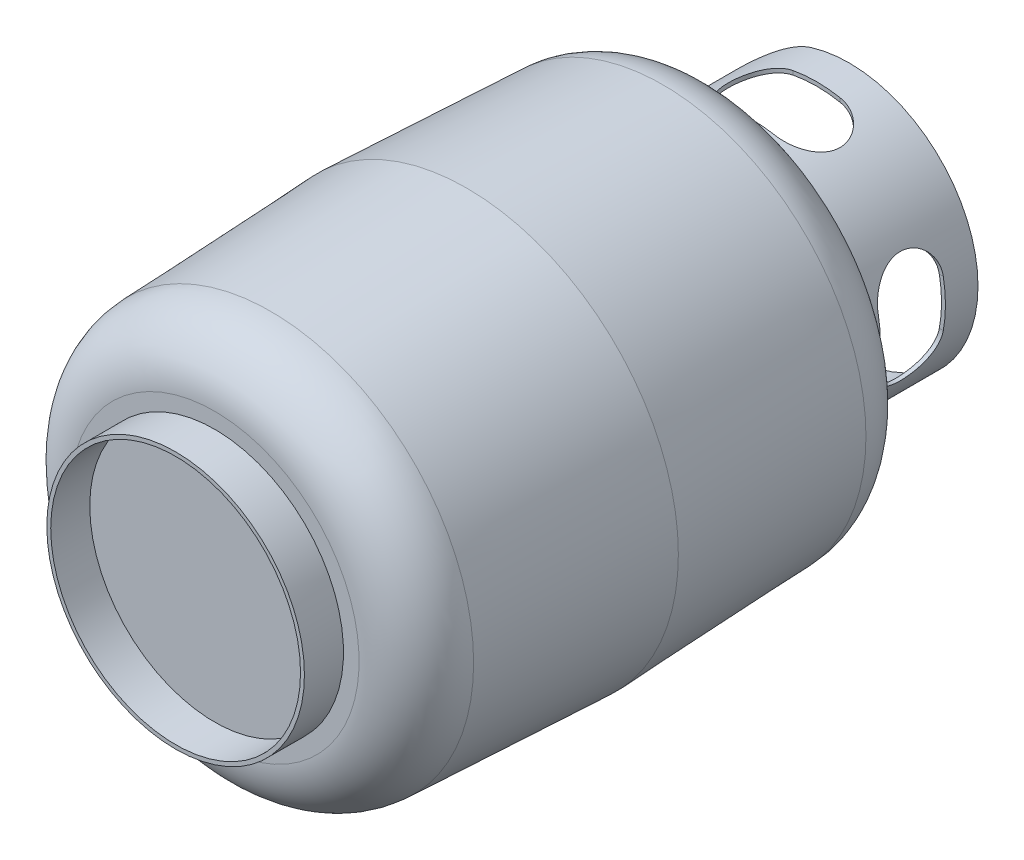
SolidWorks part; units mm, degrees
material "1060 Alloy"
ref_plane "Front Plane" through (0, 0, 0) normal (0, 0, 1) x (1, 0, 0)
ref_plane "Top Plane" through (0, 0, 0) normal (0, 1, 0) x (1, 0, 0)
ref_plane "Right Plane" through (0, 0, 0) normal (1, 0, 0) x (0, 0, -1)
sketch "Sketch1" plane through (0, 0, 0) normal (0, 1, 0) x (1, 0, 0)
  line L0 (0, 288.0587) -> (0, -288.0587) construction
  line L1 (-201.8145, 0) -> (201.8145, 0) construction
  line L2 (0, -193.75) -> (110.9626, -193.75)
  line L3 (155.9197, -150.7129) -> (162.5, 0)
  line L4 (162.5, 0) -> (155.9197, 150.7129)
  line L5 (110.9626, 193.75) -> (37, 193.75)
  line L6 (25, 205.75) -> (25, 213.75)
  line L7 (0, -189.75) -> (110.9626, -189.75)
  line L8 (0, -193.75) -> (0, 213.75) construction
  line L9 (151.9235, -150.5384) -> (158.4962, 0)
  line L10 (158.4962, 0) -> (151.9235, 150.5384)
  line L11 (110.9626, 189.75) -> (37, 189.75)
  line L12 (21, 205.75) -> (21, 213.75)
  line L13 (21, 213.75) -> (25, 213.75)
  line L14 (0, -189.75) -> (0, -193.75)
  arc A0 (155.9197, -150.7129) -> (110.9626, -193.75) centre (110.9626, -148.75) cw
  arc A1 (110.9626, 193.75) -> (155.9197, 150.7129) centre (110.9626, 148.75) cw
  arc A2 (25, 205.75) -> (37, 193.75) centre (37, 205.75) ccw
  arc A3 (151.9235, -150.5384) -> (110.9626, -189.75) centre (110.9626, -148.75) cw
  arc A4 (110.9626, 189.75) -> (151.9235, 150.5384) centre (110.9626, 148.75) cw
  arc A5 (21, 205.75) -> (37, 189.75) centre (37, 205.75) ccw
  point P4 (0, 0)
  point P8 (0, 0)
  point P16 (154.0407, 193.75)
  dimension "D3" = 45
  dimension "D5" = 12
  dimension "D8" = 301.4257
  dimension "D1" = 25
  dimension "D2" = 387.5
  dimension "D4" = 92.5
  dimension "D6" = 20
  dimension "D7" = 162.5
  dimension "D9" = 137.5
  dimension "D10" = 4
revolve "Revolve2" add sketch "Sketch1" angle 360 about L0
sketch "Sketch5" plane through (0, 0, 193.75) normal (0, 0, 1) x (1, 0, 0)
  circle A0 centre (0, 0) radius 98.9626
  circle A1 centre (0, 0) radius 95.9626
  circle A2 centre (0, 0) radius 110.9626 construction
  dimension "D1" = 12
  dimension "D2" = 3
extrude "Boss-Extrude1" add sketch "Sketch5" along normal blind 30
sketch "Sketch6" plane through (0, 0, -193.75) normal (0, 0, -1) x (-1, 0, 0)
  line L0 (-98.9626, 0) -> (98.9626, 0) construction
  line L1 (0, 98.9626) -> (0, -98.9626) construction
  line L2 (0, 0) -> (56.7626, 81.0654) construction
  line L3 (0, 0) -> (56.7626, -81.0654) construction
  line L4 (56.7626, 81.0654) -> (55.0419, 78.6079)
  line L5 (55.0419, -78.6079) -> (56.7626, -81.0654)
  arc A0 (56.7626, 81.0654) -> (56.7626, -81.0654) centre (0, 0) ccw
  arc A1 (55.0419, 78.6079) -> (55.0419, -78.6079) centre (0, 0) ccw
  circle A2 centre (0, 0) radius 110.9626 construction
  point P9 (0, 0)
  point P12 (0, 0)
  dimension "D1" = 12
  dimension "D2" = 3
  dimension "D3" = 55
extrude "Boss-Extrude2" add sketch "Sketch6" along normal blind 100
fillet "Fillet1" radius 30 2 edges at (-55.9022, 79.8367, -293.75) (-55.9022, -79.8367, -293.75)
sketch "Sketch7" plane through (0, 0, 0) normal (0, 1, 0) x (1, 0, 0)
  line L0 (0, -317.6654) -> (0, 317.6654) construction
  line L1 (310.6091, 0) -> (-310.6091, 0) construction
  line L2 (-220.5391, 243.75) -> (220.5391, 243.75) construction
  line L3 (95.9626, 293.75) -> (-27.7085, 293.75) construction
  line L4 (-18, 269.7278) -> (-18, 217.7722) construction
  line L5 (18, 269.7278) -> (18, 217.7722) construction
  line L6 (-18, 268.75) -> (18, 268.75)
  line L7 (-18, 218.75) -> (18, 218.75)
  arc A0 (-18, 268.75) -> (-18, 218.75) centre (-18, 243.75) ccw
  arc A1 (18, 218.75) -> (18, 268.75) centre (18, 243.75) ccw
  point P4 (0, 0)
  point P8 (0, 0)
  point P11 (0, 243.75)
  dimension "D3" = 50
  dimension "D1" = 50
  dimension "D2" = 18
extrude "Cut-Extrude3" cut sketch "Sketch7" against normal mid plane 310
sketch "Sketch8" plane through (0, 0, 0) normal (1, 0, 0) x (0, 0, -1)
  line L0 (-318.3277, 0) -> (318.3277, 0) construction
  line L1 (0, -285.4425) -> (0, 285.4425) construction
  line L3 (266.6699, 18) -> (209.0515, 18) construction
  line L4 (266.6699, -18) -> (209.0515, -18) construction
  line L5 (243.75, 256.3022) -> (243.75, -256.3022) construction
  line L6 (293.75, -98.9626) -> (293.75, 98.9626) construction
  line L7 (268.75, 18) -> (268.75, -18)
  line L8 (218.75, 18) -> (218.75, -18)
  arc A0 (268.75, 18) -> (218.75, 18) centre (243.75, 18) ccw
  arc A1 (268.75, -18) -> (218.75, -18) centre (243.75, -18) cw
  point P4 (0, 0)
  point P8 (0, 0)
  point P15 (243.75, 0)
  dimension "D3" = 50
  dimension "D1" = 18
  dimension "D2" = 50
extrude "Cut-Extrude4" cut sketch "Sketch8" against normal mid plane 310
equation "\"A\" = 325mm"
equation "\"B\"= 387.5mm"
